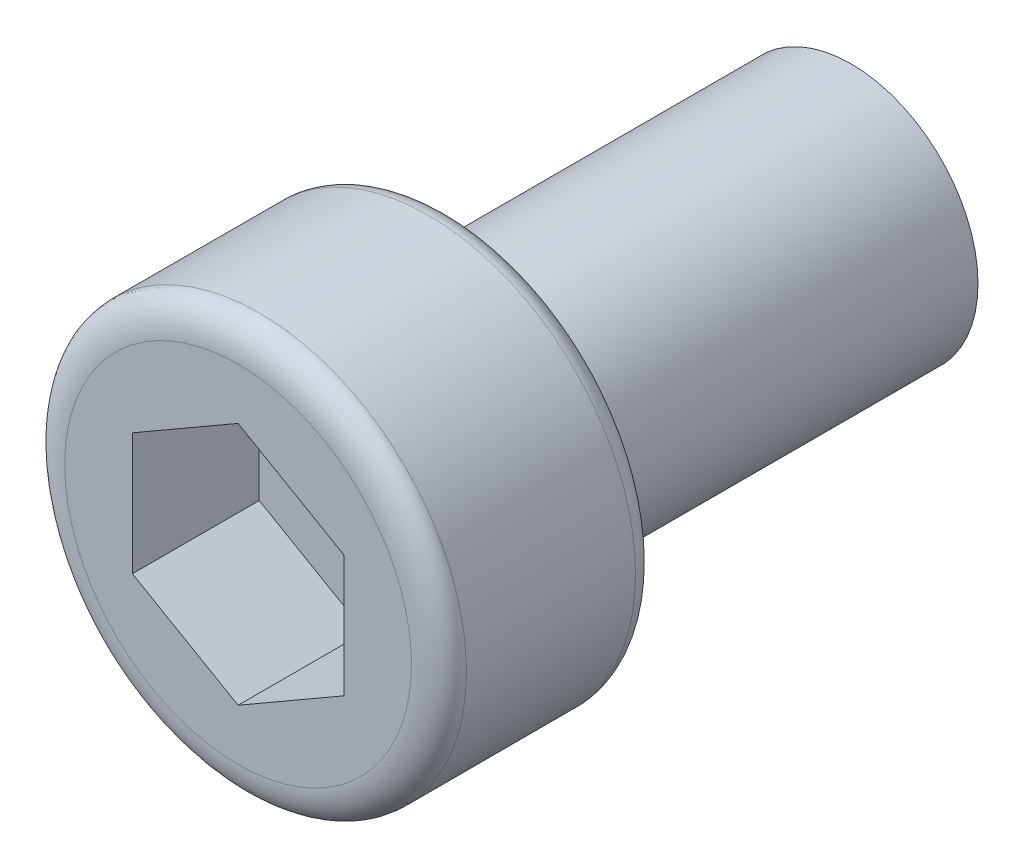
SolidWorks part; units mm, degrees
ref_plane "前视基准面" through (0, 0, 0) normal (0, 0, 1) x (1, 0, 0)
ref_plane "上视基准面" through (0, 0, 0) normal (0, 1, 0) x (1, 0, 0)
ref_plane "右视基准面" through (0, 0, 0) normal (1, 0, 0) x (0, 0, -1)
sketch "草图2" plane through (0, 0, 0) normal (1, 0, 0) x (0, 0, -1)
  line L0 (-7.5, 0) -> (-7.5, 4.9)
  line L1 (-7.5, 4.9) -> (-2.5, 4.9)
  line L2 (-2.5, 4.9) -> (-2.5, 3)
  line L3 (-2.5, 3) -> (7.5, 3)
  line L4 (7.5, 3) -> (7.5, 0)
  line L5 (7.5, 0) -> (-7.5, 0)
  dimension "D1" = 3
  dimension "D2" = 4.9
  dimension "D3" = 5
  dimension "D4" = 10
revolve "旋转1" add sketch "草图2" angle 360 about L5
fillet "圆角1" radius 0.5 1 edges at (0, 4.9, 2.5)
fillet "圆角2" radius 0.8 1 edges at (0, 4.9, 7.5) second distance 0.5 first distance on face at (0, 4.9, 7.5)
chamfer "倒角1" distance 0.5 angle 60 1 edges at (0, 3, -7.5) first distance on face at (0, 3, 2.5)
sketch "草图3" plane through (0, 0, 7.5) normal (0, 0, 1) x (1, 0, 0)
  line L1 (0, 2.8868) -> (-2.5, 1.4434)
  line L2 (-2.5, 1.4434) -> (-2.5, -1.4434)
  line L3 (-2.5, -1.4434) -> (0, -2.8868)
  line L4 (0, -2.8868) -> (2.5, -1.4434)
  line L5 (2.5, -1.4434) -> (2.5, 1.4434)
  line L6 (2.5, 1.4434) -> (0, 2.8868)
  circle A0 centre (0, 0) radius 2.5 construction
  dimension "D1" = 5
extrude "切除-拉伸1" cut sketch "草图3" against normal blind 3
